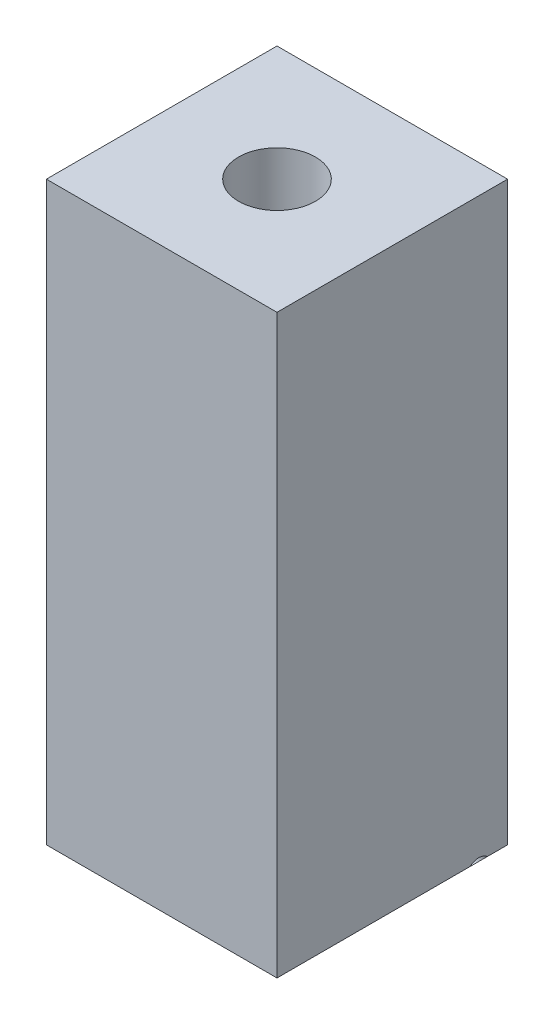
SolidWorks part; units mm, degrees
ref_plane "Спереди" through (0, 0, 0) normal (0, 0, 1) x (1, 0, 0)
ref_plane "Сверху" through (0, 0, 0) normal (0, 1, 0) x (1, 0, 0)
ref_plane "Справа" through (0, 0, 0) normal (1, 0, 0) x (0, 0, -1)
ref_plane "Плоскость1" through (-30, 0, 0) normal (-1, 0, 0) x (0, -1, 0)
sketch "Эскиз1" plane through (-30, 0, 0) normal (-1, 0, 0) x (0, -1, 0)
  line L0 (0, 66.4536) -> (0, 126.4536)
  line L1 (0, 126.4536) -> (-160, 126.4536)
  line L2 (-160, 126.4536) -> (-160, 66.4536)
  line L3 (-160, 66.4536) -> (0, 66.4536)
extrude "Бобышка-Вытянуть1" add sketch "Эскиз1" against normal blind 60
hole_wizard "Диаметр отверстия Ø6.7 (6.7)1" positions "Эскиз3" profile "Эскиз2" hole size "Ø6.7" standard "Ansi Metric"
sketch "Эскиз3" plane through (-30, 0, 0) normal (-1, 0, 0) x (0, 0, 1)
  point P0 (73.9536, 7.5)
sketch "Эскиз2" plane through (-30, 7.5, 73.9536) normal (0, 1, 0) x (0, 0, 1)
  line L0 (0, 0) -> (0, 60)
  line L1 (0, 60) -> (3.35, 60)
  line L2 (3.35, 60) -> (3.35, 0)
  line L5 (3.35, 0) -> (0, 0)
  line L11 (0, -6.35) -> (0, 107.95) construction
  dimension "Диаметр сквозного отверстия" = 6.7
  dimension "Глубина сквозного отверстия" = 60
hole_wizard "Отверстие1" positions "Эскиз5" profile "Эскиз4" legacy
sketch "Эскиз5" plane through (0, 0, 0) normal (0, -1, 0) x (-1, 0, 0)
  point P0 (0, -96.4536)
sketch "Эскиз4" plane through (0, 0, 96.4536) normal (1, 0, 0) x (0, 0, -1)
  line L0 (0, 0) -> (0, 160)
  line L1 (0, 160) -> (10, 160)
  line L2 (10, 160) -> (10, 14)
  line L3 (10, 14) -> (23.5, 14)
  line L4 (23.5, 14) -> (23.5, 0)
  line L5 (23.5, 0) -> (0, 0)
  line L6 (0, 110) -> (0, -10) construction
  dimension "Диаметр" = 20
  dimension "Глубина" = 160
  dimension "Диа. цековки" = 47
  dimension "Глуб. цековки" = 14
chamfer "Фаска1" distance 10 angle 45 4 edges at (30, 0, 96.4536) (0, 0, 126.4536) (-30, 0, 96.4536) (0, 0, 66.4536)
